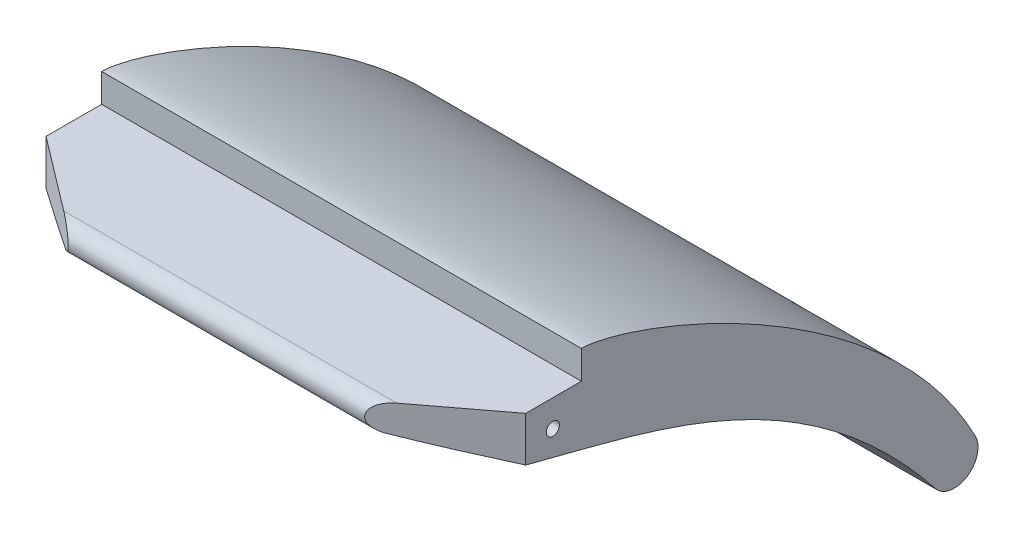
SolidWorks part; units mm, degrees
ref_plane "Front Plane" through (0, 0, 0) normal (0, 0, 1) x (1, 0, 0)
ref_plane "Top Plane" through (0, 0, 0) normal (0, 1, 0) x (1, 0, 0)
ref_plane "Right Plane" through (0, 0, 0) normal (1, 0, 0) x (0, 0, -1)
sketch "Sketch1" plane through (0, 0, 0) normal (1, 0, 0) x (0, 0, -1)
  line L0 (-14.235, 4.6355) -> (4.9116, 4.6355)
  line L1 (4.9116, 4.6355) -> (4.9116, 9.525)
  line L2 (-99.8999, 9.525) -> (-113.4123, 9.525) construction
  circle A0 centre (0, 0) radius 1.1303
  arc A1 (72.7015, -37.4179) -> (65.8572, -41.85) centre (69.0658, -39.3042) cw
  arc A2 (-14.235, 4.6355) -> (-15.0044, 0) centre (-14.235, 2.2539) ccw
  spline S0 degree 3 poles (-15.0044, 0) (9.3741, -8.3212) (39.4234, -8.5344) (65.8572, -41.85) knots 0 0 0 0 1 1 1 1
  spline S1 degree 3 poles (4.9116, 9.525) (13.3569, 9.525) (56.9145, -6.9889) (72.7015, -37.4179) knots 0 0 0 0 1 1 1 1
  dimension "D1" = 9.525
  dimension "D2" = 4.8895
extrude "Boss-Extrude1" add sketch "Sketch1" along normal blind 82.55
sketch "Sketch2" plane through (0, 4.6355, 0) normal (0, 1, 0) x (1, 0, 0)
  line L0 (0, -4.6617) -> (0, -18.4899)
  line L1 (0, 4.9116) -> (0, -14.235) construction
  line L2 (0, -18.4899) -> (18.2363, -18.4899)
  line L3 (18.2363, -18.4899) -> (0, -4.6617)
  line L4 (82.55, -4.6617) -> (82.55, -18.4899)
  line L6 (82.55, -18.4899) -> (64.3137, -18.4899)
  line L7 (64.3137, -18.4899) -> (82.55, -4.6617)
  line L8 (82.55, 4.9116) -> (82.55, -14.235) construction
extrude "Cut-Extrude1" cut sketch "Sketch2" against normal through all
